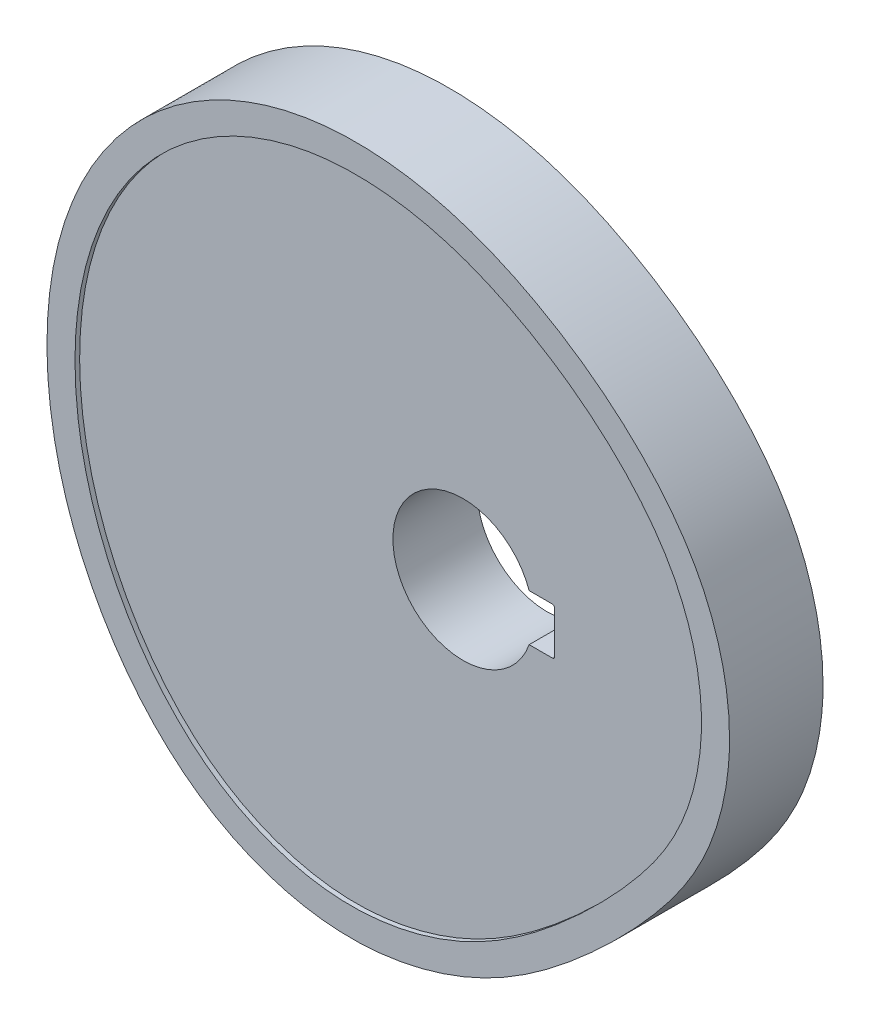
SolidWorks part; units mm, degrees
material "Plain Carbon Steel"
ref_plane "Front Plane" through (0, 0, 0) normal (0, 0, 1) x (1, 0, 0)
ref_plane "Top Plane" through (0, 0, 0) normal (0, 1, 0) x (1, 0, 0)
ref_plane "Right Plane" through (0, 0, 0) normal (1, 0, 0) x (0, 0, -1)
sketch "Displacement Sketch" plane through (0, 0, 0) normal (0, 0, 1) x (1, 0, 0)
  line L0 (0, 15) -> (0, 0) construction
  line L1 (0, 0) -> (47.1239, 0) construction
  line L2 (3.927, 0) -> (3.927, 15) construction
  line L3 (23.5619, 0) -> (23.5619, 15) construction
  line L4 (27.4889, 0) -> (27.4889, 15) construction
  line L5 (43.1969, 0) -> (43.1969, 15) construction
  line L6 (47.1239, 0) -> (47.1239, 15) construction
  line L7 (0, 0) -> (3.927, 0)
  line L8 (27.4889, 15) -> (23.5619, 15)
  line L9 (43.1969, 0) -> (47.1239, 0)
  spline S0 degree 4 poles (1.962, -0.0967) (2.0251, -0.0879) (2.1497, -0.0715) (2.3802, -0.0441) (2.7786, -0.0172) (3.1491, -0.0023) (3.8234, 0.0011) (4.1519, -0.0013) (4.7825, 0.0037) (5.2973, 0.0292) (5.8993, 0.0828) (6.4992, 0.198) (7.1843, 0.4092) (7.8229, 0.6945) (8.5028, 1.0958) (9.2434, 1.664) (10.1514, 2.5325) (11.1276, 3.6845) (12.1583, 5.0983) (13.2223, 6.6951) (14.2666, 8.3049) (15.3308, 9.9017) (16.361, 11.3155) (17.3382, 12.4675) (18.2447, 13.336) (18.9876, 13.9042) (19.6636, 14.3055) (20.2354, 14.5584) (20.6913, 14.7109) (21.0546, 14.8041) (21.3223, 14.8591) (21.5625, 14.8998) (21.7937, 14.9296) (22.0274, 14.9566) (22.3642, 14.9781) (22.6856, 14.9963) (23.3417, 15.0013) (23.6628, 14.9989) (24.3418, 15.0023) (24.7635, 15.0193) (25.1747, 15.049) (25.3985, 15.0791) (25.5259, 15.0967) knots 0 0 0 0 0 0.008159 0.016318 0.032637 0.048955 0.065274 0.0892 0.101163 0.113126 0.142767 0.163984 0.185201 0.206418 0.236195 0.268021 0.309045 0.372696 0.436348 0.5 0.563652 0.627304 0.690955 0.731979 0.763805 0.793582 0.814799 0.836016 0.846625 0.857233 0.864643 0.872053 0.879463 0.886874 0.898837 0.9108 0.934726 0.951045 0.967363 0.983682 1 1 1 1 1 construction
  spline S1 degree 4 poles (3.927, 0) (4.0838, 0) (4.3123, 0) (4.7825, 0.0037) (5.2973, 0.0292) (5.8993, 0.0828) (6.4992, 0.198) (7.1843, 0.4092) (7.8229, 0.6945) (8.5028, 1.0958) (9.2434, 1.664) (10.1514, 2.5325) (11.1276, 3.6845) (12.1583, 5.0983) (13.2223, 6.6951) (14.2666, 8.3049) (15.3308, 9.9017) (16.361, 11.3155) (17.3382, 12.4675) (18.2447, 13.336) (18.9876, 13.9042) (19.6636, 14.3055) (20.2354, 14.5584) (20.6913, 14.7109) (21.0546, 14.8041) (21.3223, 14.8591) (21.5625, 14.8998) (21.7937, 14.9296) (22.0274, 14.9566) (22.3642, 14.9781) (22.6856, 14.9963) (23.1748, 15) (23.4052, 15) (23.5619, 15) knots 0.065274 0.065274 0.065274 0.065274 0.065274 0.0892 0.101163 0.113126 0.142767 0.163984 0.185201 0.206418 0.236195 0.268021 0.309045 0.372696 0.436348 0.5 0.563652 0.627304 0.690955 0.731979 0.763805 0.793582 0.814799 0.836016 0.846625 0.857233 0.864643 0.872053 0.879463 0.886874 0.898837 0.9108 0.934726 0.934726 0.934726 0.934726 0.934726
  spline S2 degree 4 poles (25.917, 15.0967) (25.9672, 15.0879) (26.0664, 15.0716) (26.2503, 15.0442) (26.5692, 15.0173) (26.8684, 15.0023) (27.398, 14.9989) (27.6696, 15.0012) (28.1638, 14.9965) (28.4688, 14.9775) (28.7956, 14.949) (29.0691, 14.9044) (29.3652, 14.8416) (29.6303, 14.7623) (29.8895, 14.6683) (30.1363, 14.5572) (30.3781, 14.4298) (30.708, 14.2278) (31.1287, 13.9151) (31.7056, 13.3799) (32.4321, 12.5171) (33.1948, 11.3999) (33.9837, 10.0588) (34.759, 8.6207) (35.5133, 7.1717) (36.2737, 5.7258) (37.0683, 4.2981) (37.8437, 3.0586) (38.5964, 2.0494) (39.2866, 1.3197) (39.8479, 0.8516) (40.4053, 0.501) (40.8925, 0.2823) (41.3433, 0.149) (41.8164, 0.0573) (42.2412, 0.0166) (42.6103, 0.0017) (43.0977, -0.0005) (43.3551, 0.0006) (43.8251, -0.0023) (44.1115, -0.0173) (44.4386, -0.0442) (44.6184, -0.0716) (44.7185, -0.0879) (44.7693, -0.0967) knots 0 0 0 0 0 0.007472 0.014944 0.029888 0.044832 0.059777 0.081272 0.09202 0.102768 0.114604 0.126441 0.136767 0.147094 0.15742 0.167746 0.178072 0.188398 0.21612 0.247099 0.297177 0.359134 0.421092 0.48305 0.545008 0.606966 0.668924 0.730882 0.766656 0.797635 0.820922 0.841574 0.866069 0.878735 0.891402 0.915813 0.928018 0.940223 0.955168 0.970112 0.985056 0.992528 1 1 1 1 1 construction
  spline S3 degree 4 poles (27.4889, 15) (27.6137, 15) (27.7971, 15) (28.1638, 14.9965) (28.4688, 14.9775) (28.7956, 14.949) (29.0691, 14.9044) (29.3652, 14.8416) (29.6303, 14.7623) (29.8895, 14.6683) (30.1363, 14.5572) (30.3781, 14.4298) (30.708, 14.2278) (31.1287, 13.9151) (31.7056, 13.3799) (32.4321, 12.5171) (33.1948, 11.3999) (33.9837, 10.0588) (34.759, 8.6207) (35.5133, 7.1717) (36.2737, 5.7258) (37.0683, 4.2981) (37.8437, 3.0586) (38.5964, 2.0494) (39.2866, 1.3197) (39.8479, 0.8516) (40.4053, 0.501) (40.8925, 0.2823) (41.3433, 0.149) (41.8164, 0.0573) (42.2412, 0.0166) (42.6103, 0.0017) (42.9834, 0) (43.1261, 0) (43.1969, 0) knots 0.059777 0.059777 0.059777 0.059777 0.059777 0.081272 0.09202 0.102768 0.114604 0.126441 0.136767 0.147094 0.15742 0.167746 0.178072 0.188398 0.21612 0.247099 0.297177 0.359134 0.421092 0.48305 0.545008 0.606966 0.668924 0.730882 0.766656 0.797635 0.820922 0.841574 0.866069 0.878735 0.891402 0.915813 0.928018 0.940223 0.940223 0.940223 0.940223 0.940223
  dimension "D1" = 15
  dimension "D2" = 47.1239
  dimension "D3" = 3.927
  dimension "D4" = 19.635
  dimension "D5" = 3.927
  dimension "D6" = 15.708
  dimension "D7" = 3.927
sketch "Velocity Sketch" plane through (0, 0, 0) normal (0, 0, 1) x (1, 0, 0)
  line L0 (0, -15) -> (0, -65) construction
  line L1 (0, -40) -> (47.1239, -40) construction
  line L2 (3.927, -15) -> (3.927, -65) construction
  line L3 (23.5619, -15) -> (23.5619, -65) construction
  line L4 (27.4889, -15) -> (27.4889, -65) construction
  line L5 (43.1969, -15) -> (43.1969, -65) construction
  line L6 (47.1239, -15) -> (47.1239, -65) construction
  line L7 (0, -40) -> (3.927, -40)
  line L8 (23.5619, -40) -> (27.4889, -40)
  line L9 (43.1969, -40) -> (47.1239, -40)
  spline S0 degree 4 poles (1.9635, -38.9057) (2.0257, -38.9728) (2.1526, -39.1046) (2.3179, -39.263) (2.5282, -39.4396) (2.7124, -39.5752) (2.8656, -39.6755) (3.0312, -39.7696) (3.21, -39.8541) (3.378, -39.9155) (3.5323, -39.9566) (3.6606, -39.9808) (3.7704, -39.9939) (3.8976, -40.0012) (3.9765, -40.0003) (4.0914, -39.9931) (4.2047, -39.9788) (4.3113, -39.9585) (4.4273, -39.9287) (4.5497, -39.8882) (4.6855, -39.8341) (4.8338, -39.7637) (5.0005, -39.6692) (5.2228, -39.5203) (5.4703, -39.3234) (5.7369, -39.0742) (6.0182, -38.7713) (6.2635, -38.4767) (6.4789, -38.1966) (6.7119, -37.8755) (6.9601, -37.5119) (7.2378, -37.08) (7.6188, -36.4531) (8.0578, -35.69) (8.695, -34.5334) (9.3923, -33.2428) (10.1106, -31.9631) (10.8521, -30.798) (11.4447, -29.9912) (12.0701, -29.306) (12.6823, -28.8165) (13.3594, -28.5265) (13.9982, -28.5224) (14.4931, -28.6816) (14.9938, -28.9673) (15.4821, -29.3759) (16.0352, -29.9801) (16.6301, -30.7877) (17.3726, -31.9534) (18.0917, -33.2337) (18.7893, -34.5249) (19.4267, -35.6821) (19.8657, -36.4456) (20.2468, -37.073) (20.5641, -37.567) (20.8732, -38.0148) (21.1744, -38.4151) (21.4671, -38.7672) (21.7491, -39.0713) (22.0564, -39.3589) (22.3514, -39.5861) (22.6045, -39.7396) (22.8026, -39.8338) (22.9386, -39.888) (23.0611, -39.9286) (23.1771, -39.9584) (23.2842, -39.9788) (23.3789, -39.9907) (23.4581, -39.9971) (23.5401, -40.0006) (23.6106, -40) (23.7191, -39.9939) (23.8283, -39.9808) (23.9566, -39.9566) (24.111, -39.9155) (24.322, -39.8383) (24.5805, -39.7075) (24.8544, -39.5266) (25.138, -39.2946) (25.3363, -39.1046) (25.4632, -38.9728) (25.5254, -38.9057) knots 0 0 0 0 0 0.010194 0.020387 0.025484 0.030581 0.035677 0.040774 0.046689 0.052603 0.05556 0.058517 0.061474 0.064432 0.068544 0.0706 0.072656 0.076768 0.08088 0.083926 0.086973 0.093066 0.099159 0.105252 0.116762 0.128271 0.13978 0.15129 0.159464 0.167638 0.183987 0.200336 0.216684 0.249382 0.282079 0.347474 0.380171 0.412868 0.435887 0.458906 0.483278 0.499726 0.516191 0.528398 0.540605 0.563699 0.586794 0.619507 0.652221 0.717647 0.750361 0.783074 0.799431 0.815787 0.832144 0.8485 0.860048 0.871595 0.883143 0.89469 0.906897 0.913 0.916052 0.919104 0.92322 0.927336 0.929394 0.931452 0.93351 0.935568 0.938526 0.941483 0.94444 0.947397 0.953311 0.959226 0.969419 0.979613 0.989806 1 1 1 1 1 construction
  spline S1 degree 4 poles (3.927, -40) (3.9591, -40) (4.0069, -39.9984) (4.0914, -39.9931) (4.2047, -39.9788) (4.3113, -39.9585) (4.4273, -39.9287) (4.5497, -39.8882) (4.6855, -39.8341) (4.8338, -39.7637) (5.0005, -39.6692) (5.2228, -39.5203) (5.4703, -39.3234) (5.7369, -39.0742) (6.0182, -38.7713) (6.2635, -38.4767) (6.4789, -38.1966) (6.7119, -37.8755) (6.9601, -37.5119) (7.2378, -37.08) (7.6188, -36.4531) (8.0578, -35.69) (8.695, -34.5334) (9.3923, -33.2428) (10.1106, -31.9631) (10.8521, -30.798) (11.4447, -29.9912) (12.0701, -29.306) (12.6823, -28.8165) (13.3594, -28.5265) (13.9982, -28.5224) (14.4931, -28.6816) (14.9938, -28.9673) (15.4821, -29.3759) (16.0352, -29.9801) (16.6301, -30.7877) (17.3726, -31.9534) (18.0917, -33.2337) (18.7893, -34.5249) (19.4267, -35.6821) (19.8657, -36.4456) (20.2468, -37.073) (20.5641, -37.567) (20.8732, -38.0148) (21.1744, -38.4151) (21.4671, -38.7672) (21.7491, -39.0713) (22.0564, -39.3589) (22.3514, -39.5861) (22.6045, -39.7396) (22.8026, -39.8338) (22.9386, -39.888) (23.0611, -39.9286) (23.1771, -39.9584) (23.2842, -39.9788) (23.3789, -39.9907) (23.4581, -39.9971) (23.5136, -39.9995) (23.5459, -40) (23.5619, -40) knots 0.064432 0.064432 0.064432 0.064432 0.064432 0.068544 0.0706 0.072656 0.076768 0.08088 0.083926 0.086973 0.093066 0.099159 0.105252 0.116762 0.128271 0.13978 0.15129 0.159464 0.167638 0.183987 0.200336 0.216684 0.249382 0.282079 0.347474 0.380171 0.412868 0.435887 0.458906 0.483278 0.499726 0.516191 0.528398 0.540605 0.563699 0.586794 0.619507 0.652221 0.717647 0.750361 0.783074 0.799431 0.815787 0.832144 0.8485 0.860048 0.871595 0.883143 0.89469 0.906897 0.913 0.916052 0.919104 0.92322 0.927336 0.929394 0.931452 0.93351 0.935568 0.935568 0.935568 0.935568 0.935568
  spline S2 degree 4 poles (25.9181, -41.3678) (25.969, -41.2822) (26.0474, -41.155) (26.1567, -40.9884) (26.3034, -40.7872) (26.428, -40.6317) (26.5612, -40.4834) (26.7044, -40.3447) (26.8491, -40.2282) (26.9938, -40.1353) (27.1202, -40.0746) (27.2225, -40.0387) (27.3087, -40.0172) (27.3821, -40.0055) (27.4558, -39.9999) (27.5062, -39.9994) (27.5651, -40.003) (27.6216, -40.0095) (27.6752, -40.0191) (27.7266, -40.0316) (27.79, -40.0509) (27.8853, -40.0869) (28.0075, -40.1485) (28.1907, -40.2707) (28.3839, -40.4445) (28.5692, -40.6505) (28.7482, -40.8845) (28.8972, -41.1024) (29.0371, -41.3263) (29.1693, -41.5547) (29.3267, -41.8447) (29.5183, -42.2252) (29.738, -42.6988) (29.9816, -43.2668) (30.2236, -43.8681) (30.5135, -44.6245) (30.8469, -45.5378) (31.2234, -46.6076) (31.6487, -47.832) (32.0801, -49.0542) (32.4735, -50.118) (32.8326, -51.0215) (33.142, -51.7326) (33.3888, -52.2556) (33.6408, -52.7378) (33.8982, -53.1762) (34.223, -53.6432) (34.5556, -54.0066) (34.9078, -54.2495) (35.2458, -54.3293) (35.458, -54.327) (35.7081, -54.2632) (35.9731, -54.1157) (36.2611, -53.8668) (36.5554, -53.5158) (36.8301, -53.1086) (37.0915, -52.6536) (37.3438, -52.1599) (37.5898, -51.63) (37.8954, -50.918) (38.2495, -50.0196) (38.6386, -48.9625) (39.0662, -47.7483) (39.4887, -46.5322) (39.8632, -45.4699) (40.1952, -44.5632) (40.4842, -43.8123) (40.7255, -43.2156) (40.9683, -42.653) (41.187, -42.1848) (41.3776, -41.8095) (41.5335, -41.5246) (41.6646, -41.3002) (41.8032, -41.0803) (41.9509, -40.8664) (42.1281, -40.6369) (42.3115, -40.4352) (42.5023, -40.2652) (42.6833, -40.1457) (42.8038, -40.0854) (42.8984, -40.0501) (42.9739, -40.0273) (43.0476, -40.0102) (43.1489, -40) (43.2166, -39.9988) (43.3032, -40.0055) (43.3772, -40.0172) (43.4633, -40.0387) (43.5656, -40.0746) (43.6921, -40.1353) (43.8367, -40.2282) (43.9814, -40.3447) (44.1247, -40.4834) (44.2578, -40.6317) (44.3824, -40.7872) (44.5292, -40.9884) (44.6384, -41.155) (44.7169, -41.2822) (44.7677, -41.3678) knots 0 0 0 0 0 0.010463 0.015694 0.020925 0.026157 0.031388 0.03662 0.041851 0.045635 0.049419 0.051311 0.053203 0.055095 0.056987 0.058388 0.05979 0.061191 0.062592 0.063993 0.065395 0.068197 0.073266 0.078335 0.088472 0.095404 0.102336 0.109267 0.116199 0.123131 0.130063 0.143926 0.160948 0.17797 0.194992 0.212014 0.246057 0.280101 0.314145 0.348188 0.382232 0.399254 0.416276 0.429638 0.443 0.456362 0.469724 0.489196 0.494701 0.500206 0.505766 0.511326 0.521544 0.531762 0.545538 0.559313 0.573088 0.586864 0.60377 0.620676 0.654487 0.688299 0.722111 0.755922 0.789734 0.80664 0.823546 0.840451 0.857357 0.871007 0.877832 0.884657 0.891482 0.898307 0.905132 0.911957 0.921925 0.926909 0.931893 0.934673 0.936063 0.937453 0.940233 0.943013 0.944905 0.946797 0.948689 0.950581 0.954365 0.958149 0.96338 0.968612 0.973843 0.979075 0.984306 0.989537 1 1 1 1 1 construction
  spline S3 degree 4 poles (27.4889, -40) (27.5008, -40) (27.5245, -40.0005) (27.5651, -40.003) (27.6216, -40.0095) (27.6752, -40.0191) (27.7266, -40.0316) (27.79, -40.0509) (27.8853, -40.0869) (28.0075, -40.1485) (28.1907, -40.2707) (28.3839, -40.4445) (28.5692, -40.6505) (28.7482, -40.8845) (28.8972, -41.1024) (29.0371, -41.3263) (29.1693, -41.5547) (29.3267, -41.8447) (29.5183, -42.2252) (29.738, -42.6988) (29.9816, -43.2668) (30.2236, -43.8681) (30.5135, -44.6245) (30.8469, -45.5378) (31.2234, -46.6076) (31.6487, -47.832) (32.0801, -49.0542) (32.4735, -50.118) (32.8326, -51.0215) (33.142, -51.7326) (33.3888, -52.2556) (33.6408, -52.7378) (33.8982, -53.1762) (34.223, -53.6432) (34.5556, -54.0066) (34.9078, -54.2495) (35.2458, -54.3293) (35.458, -54.327) (35.7081, -54.2632) (35.9731, -54.1157) (36.2611, -53.8668) (36.5554, -53.5158) (36.8301, -53.1086) (37.0915, -52.6536) (37.3438, -52.1599) (37.5898, -51.63) (37.8954, -50.918) (38.2495, -50.0196) (38.6386, -48.9625) (39.0662, -47.7483) (39.4887, -46.5322) (39.8632, -45.4699) (40.1952, -44.5632) (40.4842, -43.8123) (40.7255, -43.2156) (40.9683, -42.653) (41.187, -42.1848) (41.3776, -41.8095) (41.5335, -41.5246) (41.6646, -41.3002) (41.8032, -41.0803) (41.9509, -40.8664) (42.1281, -40.6369) (42.3115, -40.4352) (42.5023, -40.2652) (42.6833, -40.1457) (42.8038, -40.0854) (42.8984, -40.0501) (42.9739, -40.0273) (43.0476, -40.0102) (43.1272, -40.0021) (43.1735, -40) (43.1969, -40) knots 0.056987 0.056987 0.056987 0.056987 0.056987 0.058388 0.05979 0.061191 0.062592 0.063993 0.065395 0.068197 0.073266 0.078335 0.088472 0.095404 0.102336 0.109267 0.116199 0.123131 0.130063 0.143926 0.160948 0.17797 0.194992 0.212014 0.246057 0.280101 0.314145 0.348188 0.382232 0.399254 0.416276 0.429638 0.443 0.456362 0.469724 0.489196 0.494701 0.500206 0.505766 0.511326 0.521544 0.531762 0.545538 0.559313 0.573088 0.586864 0.60377 0.620676 0.654487 0.688299 0.722111 0.755922 0.789734 0.80664 0.823546 0.840451 0.857357 0.871007 0.877832 0.884657 0.891482 0.898307 0.905132 0.911957 0.921925 0.926909 0.931893 0.934673 0.936063 0.937453 0.940233 0.943013 0.943013 0.943013 0.943013 0.943013
  point P15 (23.5619, -40)
  point P27 (43.1969, -40)
  point P28 (3.927, -40)
  point P35 (27.4889, -40)
  dimension "D1" = 50
  dimension "D2" = 15
  dimension "D3" = 47.1239
sketch "Acceleration Sketch" plane through (0, 0, 0) normal (0, 0, 1) x (1, 0, 0)
  line L0 (0, -80) -> (0, -130) construction
  line L1 (0, -15) -> (0, -65) construction
  line L2 (3.927, -80) -> (3.927, -130) construction
  line L3 (23.5619, -80) -> (23.5619, -130) construction
  line L4 (27.4889, -80) -> (27.4889, -130) construction
  line L5 (43.1969, -80) -> (43.1969, -130) construction
  line L6 (47.1239, -80) -> (47.1239, -130) construction
  line L7 (0, -105) -> (47.1239, -105) construction
  spline S0 degree 4 poles (2.572, -110.7775) (2.5826, -110.7352) (2.6049, -110.6462) (2.6568, -110.4348) (2.7247, -110.1667) (2.8631, -109.5866) (2.9168, -109.376) (3.1103, -108.5487) (3.2451, -107.9915) (3.7647, -105.7173) (3.9235, -105.0128) (4.4418, -102.7383) (4.726, -101.5165) (5.0905, -99.9824) (5.4257, -98.6411) (5.7628, -97.3573) (6.0541, -96.3347) (6.324, -95.4451) (6.5477, -94.7627) (6.7807, -94.1024) (7.0182, -93.4965) (7.2387, -92.994) (7.4321, -92.6044) (7.6103, -92.2868) (7.7652, -92.0405) (7.9385, -91.8029) (8.1364, -91.5783) (8.3751, -91.3792) (8.6628, -91.239) (9.0399, -91.2355) (9.3821, -91.4294) (9.658, -91.7026) (9.9031, -92.031) (10.1006, -92.3508) (10.3757, -92.8619) (10.6941, -93.5774) (11.0415, -94.5007) (11.4096, -95.6315) (11.7539, -96.8019) (12.0819, -98.0088) (12.4807, -99.5681) (12.9408, -101.482) (13.4552, -103.72) (14.0337, -106.28) (14.5481, -108.518) (15.0082, -110.4319) (15.4071, -111.9912) (15.735, -113.1981) (16.0793, -114.3685) (16.4474, -115.4993) (16.7948, -116.4226) (17.1133, -117.1381) (17.3883, -117.6492) (17.5858, -117.969) (17.831, -118.2974) (18.1068, -118.5706) (18.449, -118.7645) (18.8261, -118.761) (19.1138, -118.6208) (19.3525, -118.4218) (19.5505, -118.197) (19.7664, -117.9009) (19.991, -117.5251) (20.221, -117.0728) (20.4706, -116.5036) (20.7083, -115.8976) (20.9412, -115.2374) (21.1649, -114.5549) (21.4349, -113.6653) (21.7261, -112.6427) (22.0633, -111.3589) (22.3985, -110.0176) (22.763, -108.4835) (23.0471, -107.2617) (23.5654, -104.9872) (23.7242, -104.2827) (24.2438, -102.0085) (24.3787, -101.4513) (24.5722, -100.624) (24.6258, -100.4134) (24.7642, -99.8333) (24.8321, -99.5652) (24.884, -99.3538) (24.9063, -99.2648) (24.917, -99.2225) knots 0 0 0 0 0 0.002588 0.005177 0.010354 0.020707 0.025884 0.031061 0.041414 0.082829 0.103192 0.123556 0.14392 0.164284 0.184648 0.205012 0.215194 0.225376 0.235558 0.24574 0.253858 0.261975 0.266034 0.270093 0.274152 0.278211 0.282468 0.286725 0.291483 0.295696 0.302677 0.307932 0.313188 0.318443 0.323699 0.340297 0.356895 0.373493 0.390091 0.408409 0.426727 0.463364 0.5 0.536636 0.573273 0.591591 0.609909 0.626507 0.643105 0.659703 0.676301 0.681557 0.686812 0.692068 0.697323 0.704304 0.708517 0.713275 0.717532 0.721789 0.725848 0.729907 0.738025 0.746142 0.75426 0.764442 0.774624 0.784806 0.794988 0.815352 0.835716 0.85608 0.876444 0.896808 0.917171 0.958586 0.968939 0.974116 0.979293 0.989646 0.994823 0.997412 1 1 1 1 1 construction
  spline S1 degree 4 poles (3.927, -105) (3.9944, -104.7033) (4.1329, -104.0938) (4.4418, -102.7383) (4.726, -101.5165) (5.0905, -99.9824) (5.4257, -98.6411) (5.7628, -97.3573) (6.0541, -96.3347) (6.324, -95.4451) (6.5477, -94.7627) (6.7807, -94.1024) (7.0182, -93.4965) (7.2387, -92.994) (7.4321, -92.6044) (7.6103, -92.2868) (7.7652, -92.0405) (7.9385, -91.8029) (8.1364, -91.5783) (8.3751, -91.3792) (8.6628, -91.239) (9.0399, -91.2355) (9.3821, -91.4294) (9.658, -91.7026) (9.9031, -92.031) (10.1006, -92.3508) (10.3757, -92.8619) (10.6941, -93.5774) (11.0415, -94.5007) (11.4096, -95.6315) (11.7539, -96.8019) (12.0819, -98.0088) (12.4807, -99.5681) (12.9408, -101.482) (13.4552, -103.72) (14.0337, -106.28) (14.5481, -108.518) (15.0082, -110.4319) (15.4071, -111.9912) (15.735, -113.1981) (16.0793, -114.3685) (16.4474, -115.4993) (16.7948, -116.4226) (17.1133, -117.1381) (17.3883, -117.6492) (17.5858, -117.969) (17.831, -118.2974) (18.1068, -118.5706) (18.449, -118.7645) (18.8261, -118.761) (19.1138, -118.6208) (19.3525, -118.4218) (19.5505, -118.197) (19.7664, -117.9009) (19.991, -117.5251) (20.221, -117.0728) (20.4706, -116.5036) (20.7083, -115.8976) (20.9412, -115.2374) (21.1649, -114.5549) (21.4349, -113.6653) (21.7261, -112.6427) (22.0633, -111.3589) (22.3985, -110.0176) (22.763, -108.4835) (23.0471, -107.2617) (23.356, -105.9062) (23.4945, -105.2967) (23.5619, -105) knots 0.082829 0.082829 0.082829 0.082829 0.082829 0.103192 0.123556 0.14392 0.164284 0.184648 0.205012 0.215194 0.225376 0.235558 0.24574 0.253858 0.261975 0.266034 0.270093 0.274152 0.278211 0.282468 0.286725 0.291483 0.295696 0.302677 0.307932 0.313188 0.318443 0.323699 0.340297 0.356895 0.373493 0.390091 0.408409 0.426727 0.463364 0.5 0.536636 0.573273 0.591591 0.609909 0.626507 0.643105 0.659703 0.676301 0.681557 0.686812 0.692068 0.697323 0.704304 0.708517 0.713275 0.717532 0.721789 0.725848 0.729907 0.738025 0.746142 0.75426 0.764442 0.774624 0.784806 0.794988 0.815352 0.835716 0.85608 0.876444 0.896808 0.917171 0.917171 0.917171 0.917171 0.917171
  spline S2 degree 4 poles (26.4484, -96.3102) (26.5118, -96.8222) (26.5658, -97.2281) (26.8032, -99.1812) (26.9742, -100.5869) (27.3892, -104.1392) (27.5686, -105.6882) (27.9878, -109.2775) (28.2426, -111.3928) (28.6075, -114.3425) (28.9332, -116.7713) (29.3318, -119.5372) (29.6889, -121.6296) (30.0509, -123.449) (30.3524, -124.5941) (30.5472, -125.2296) (30.7103, -125.6432) (30.821, -125.8896) (30.926, -126.0792) (31.0123, -126.2131) (31.0985, -126.3183) (31.1798, -126.3936) (31.2441, -126.4375) (31.2991, -126.4643) (31.3487, -126.4798) (31.3966, -126.4868) (31.4431, -126.4862) (31.491, -126.4779) (31.541, -126.4609) (31.5967, -126.4322) (31.6626, -126.3849) (31.7478, -126.3032) (31.8681, -126.1482) (32.0585, -125.8141) (32.3727, -125.0186) (32.7489, -123.6119) (33.1471, -121.6395) (33.5462, -119.2173) (33.9186, -116.6385) (34.2594, -114.0551) (34.5809, -111.4694) (34.8901, -108.8821) (35.1927, -106.2941) (35.4931, -103.7059) (35.7957, -101.1179) (36.1049, -98.5306) (36.4264, -95.9449) (36.7673, -93.3615) (37.1397, -90.7827) (37.5387, -88.3605) (37.9369, -86.3881) (38.3131, -84.9814) (38.6274, -84.1859) (38.8178, -83.8518) (38.9381, -83.6968) (39.0232, -83.6151) (39.0891, -83.5678) (39.1448, -83.5391) (39.1948, -83.5221) (39.2428, -83.5138) (39.2893, -83.5132) (39.3371, -83.5202) (39.3867, -83.5357) (39.4417, -83.5624) (39.506, -83.6068) (39.5872, -83.6808) (39.7, -83.8211) (39.8275, -84.031) (39.9606, -84.3179) (40.1387, -84.7711) (40.3334, -85.4056) (40.635, -86.5512) (40.9969, -88.3703) (41.354, -90.4629) (41.7526, -93.2287) (42.0783, -95.6575) (42.4432, -98.6072) (42.6981, -100.7225) (43.1172, -104.3118) (43.2966, -105.8608) (43.7116, -109.4131) (43.8826, -110.8188) (44.12, -112.7719) (44.174, -113.1778) (44.2375, -113.6898) knots 0 0 0 0 0 0.013744 0.027488 0.054976 0.082464 0.107561 0.132658 0.157755 0.182852 0.207948 0.233045 0.258142 0.266928 0.275713 0.279145 0.282576 0.284145 0.285714 0.287455 0.28853 0.289309 0.289879 0.290393 0.290836 0.291269 0.291702 0.292145 0.29267 0.293258 0.294064 0.295205 0.297118 0.300661 0.308565 0.327485 0.35213 0.376775 0.40142 0.426065 0.45071 0.475355 0.5 0.524645 0.54929 0.573935 0.59858 0.623225 0.64787 0.672515 0.691435 0.699339 0.702882 0.704795 0.705936 0.706742 0.70733 0.707855 0.708298 0.708731 0.709164 0.709607 0.710121 0.710691 0.71147 0.712545 0.714286 0.717424 0.720855 0.724287 0.733072 0.741858 0.766955 0.792052 0.817148 0.842245 0.867342 0.892439 0.917536 0.945024 0.972512 0.986256 1 1 1 1 1 construction
  spline S3 degree 4 poles (27.4889, -105) (27.553, -105.5502) (27.6807, -106.6482) (27.9878, -109.2775) (28.2426, -111.3928) (28.6075, -114.3425) (28.9332, -116.7713) (29.3318, -119.5372) (29.6889, -121.6296) (30.0509, -123.449) (30.3524, -124.5941) (30.5472, -125.2296) (30.7103, -125.6432) (30.821, -125.8896) (30.926, -126.0792) (31.0123, -126.2131) (31.0985, -126.3183) (31.1798, -126.3936) (31.2441, -126.4375) (31.2991, -126.4643) (31.3487, -126.4798) (31.3966, -126.4868) (31.4431, -126.4862) (31.491, -126.4779) (31.541, -126.4609) (31.5967, -126.4322) (31.6626, -126.3849) (31.7478, -126.3032) (31.8681, -126.1482) (32.0585, -125.8141) (32.3727, -125.0186) (32.7489, -123.6119) (33.1471, -121.6395) (33.5462, -119.2173) (33.9186, -116.6385) (34.2594, -114.0551) (34.5809, -111.4694) (34.8901, -108.8821) (35.1927, -106.2941) (35.4931, -103.7059) (35.7957, -101.1179) (36.1049, -98.5306) (36.4264, -95.9449) (36.7673, -93.3615) (37.1397, -90.7827) (37.5387, -88.3605) (37.9369, -86.3881) (38.3131, -84.9814) (38.6274, -84.1859) (38.8178, -83.8518) (38.9381, -83.6968) (39.0232, -83.6151) (39.0891, -83.5678) (39.1448, -83.5391) (39.1948, -83.5221) (39.2428, -83.5138) (39.2893, -83.5132) (39.3371, -83.5202) (39.3867, -83.5357) (39.4417, -83.5624) (39.506, -83.6068) (39.5872, -83.6808) (39.7, -83.8211) (39.8275, -84.031) (39.9606, -84.3179) (40.1387, -84.7711) (40.3334, -85.4056) (40.635, -86.5512) (40.9969, -88.3703) (41.354, -90.4629) (41.7526, -93.2287) (42.0783, -95.6575) (42.4432, -98.6072) (42.6981, -100.7225) (43.0051, -103.3518) (43.1329, -104.4498) (43.1969, -105) knots 0.082464 0.082464 0.082464 0.082464 0.082464 0.107561 0.132658 0.157755 0.182852 0.207948 0.233045 0.258142 0.266928 0.275713 0.279145 0.282576 0.284145 0.285714 0.287455 0.28853 0.289309 0.289879 0.290393 0.290836 0.291269 0.291702 0.292145 0.29267 0.293258 0.294064 0.295205 0.297118 0.300661 0.308565 0.327485 0.35213 0.376775 0.40142 0.426065 0.45071 0.475355 0.5 0.524645 0.54929 0.573935 0.59858 0.623225 0.64787 0.672515 0.691435 0.699339 0.702882 0.704795 0.705936 0.706742 0.70733 0.707855 0.708298 0.708731 0.709164 0.709607 0.710121 0.710691 0.71147 0.712545 0.714286 0.717424 0.720855 0.724287 0.733072 0.741858 0.766955 0.792052 0.817148 0.842245 0.867342 0.892439 0.917536 0.917536 0.917536 0.917536 0.917536
  point P30 (3.927, -105)
  dimension "D1" = 15
sketch "Cam Profile Sketch" plane through (0, 0, 0) normal (0, 0, 1) x (1, 0, 0)
  line L0 (-49, 0) -> (-93, 0) construction
  line L3 (-49, 0) -> (-87.1051, -22) construction
  circle A1 centre (-49, 0) radius 29 construction
  arc A2 (-93, 0) -> (-87.1051, -22) centre (-49, 0) ccw
  arc A3 (-23.8853, -14.5) -> (-23.8853, 14.5) centre (-49, 0) ccw
  spline S0 degree 4 poles (-21.0816, 7.4807) (-21.1347, 7.7136) (-21.2473, 8.178) (-21.4357, 8.8697) (-21.7242, 9.7809) (-22.0073, 10.5659) (-22.2705, 11.2287) (-22.5025, 11.7733) (-22.6947, 12.2028) (-22.8944, 12.6284) (-23.1031, 13.0532) (-23.2883, 13.415) (-23.4527, 13.7251) (-23.6023, 13.9987) (-23.726, 14.2207) (-23.8638, 14.464) (-23.992, 14.6844) (-24.2319, 15.0878) (-24.4645, 15.4634) (-24.7034, 15.8366) (-24.9512, 16.2123) (-25.2035, 16.5831) (-25.4607, 16.9499) (-25.7512, 17.3524) (-26.2677, 18.0453) (-27.1324, 19.1368) (-28.4165, 20.6093) (-30.1456, 22.3683) (-31.9522, 24.0003) (-33.682, 25.4157) (-35.2829, 26.6203) (-36.7346, 27.637) (-38.214, 28.6) (-39.7256, 29.5117) (-41.2684, 30.3695) (-43.2348, 31.3707) (-45.6528, 32.452) (-48.5535, 33.523) (-51.6032, 34.3581) (-54.3423, 34.8797) (-57.1097, 35.211) (-59.8951, 35.3457) (-63.056, 35.2217) (-66.5557, 34.7132) (-69.9807, 33.8313) (-73.2889, 32.5802) (-76.4387, 30.9712) (-79.4088, 29.0105) (-82.1582, 26.7166) (-84.6496, 24.1145) (-86.8505, 21.2354) (-88.7264, 18.1351) (-90.2072, 14.9786) (-91.2012, 12.1859) (-91.847, 9.8314) (-92.2209, 8.1094) (-92.439, 6.9089) (-92.5993, 5.859) (-92.7156, 4.9622) (-92.7998, 4.1755) (-92.8596, 3.4999) (-92.9013, 2.9365) (-92.9298, 2.4854) (-92.9534, 2.0327) (-92.9723, 1.5812) (-92.9864, 1.1389) (-92.9957, 0.6708) (-93.0008, 0.1194) (-93.0002, -0.2419) (-92.9923, -0.953) (-92.9757, -1.5075) (-92.9508, -2.1317) (-92.9179, -2.734) (-92.877, -3.3425) (-92.8281, -3.9481) (-92.7715, -4.5539) (-92.7071, -5.1586) (-92.6171, -5.9135) (-92.4941, -6.8175) (-92.3525, -7.7188) (-92.193, -8.6171) (-92.0772, -9.2141) (-92.017, -9.5122) (-91.9863, -9.6611) knots 0 0 0 0 0 0.008336 0.016672 0.025009 0.033345 0.03745 0.041556 0.045661 0.049766 0.053872 0.057977 0.06003 0.062083 0.064135 0.066188 0.070099 0.07401 0.07792 0.081831 0.085742 0.089653 0.093564 0.097475 0.103059 0.11981 0.142146 0.165611 0.189076 0.204719 0.220116 0.235513 0.25091 0.266306 0.281703 0.2971 0.327893 0.358686 0.38948 0.407291 0.425102 0.455895 0.486688 0.517482 0.548275 0.579069 0.609862 0.640655 0.672207 0.70376 0.735312 0.766864 0.798416 0.82521 0.838607 0.852004 0.859892 0.86778 0.875668 0.883556 0.8875 0.891444 0.895388 0.899332 0.903276 0.90722 0.911164 0.915108 0.920414 0.92572 0.931025 0.936331 0.941637 0.946943 0.952248 0.957554 0.96286 0.968166 0.978777 0.989389 0.994694 1 1 1 1 1 construction
  spline S1 degree 4 poles (-23.8853, 14.5) (-23.9328, 14.5824) (-24.0277, 14.7445) (-24.2319, 15.0878) (-24.4645, 15.4634) (-24.7034, 15.8366) (-24.9512, 16.2123) (-25.2035, 16.5831) (-25.4607, 16.9499) (-25.7512, 17.3524) (-26.2677, 18.0453) (-27.1324, 19.1368) (-28.4165, 20.6093) (-30.1456, 22.3683) (-31.9522, 24.0003) (-33.682, 25.4157) (-35.2829, 26.6203) (-36.7346, 27.637) (-38.214, 28.6) (-39.7256, 29.5117) (-41.2684, 30.3695) (-43.2348, 31.3707) (-45.6528, 32.452) (-48.5535, 33.523) (-51.6032, 34.3581) (-54.3423, 34.8797) (-57.1097, 35.211) (-59.8951, 35.3457) (-63.056, 35.2217) (-66.5557, 34.7132) (-69.9807, 33.8313) (-73.2889, 32.5802) (-76.4387, 30.9712) (-79.4088, 29.0105) (-82.1582, 26.7166) (-84.6496, 24.1145) (-86.8505, 21.2354) (-88.7264, 18.1351) (-90.2072, 14.9786) (-91.2012, 12.1859) (-91.847, 9.8314) (-92.2209, 8.1094) (-92.439, 6.9089) (-92.5993, 5.859) (-92.7156, 4.9622) (-92.7998, 4.1755) (-92.8596, 3.4999) (-92.9013, 2.9365) (-92.9298, 2.4854) (-92.9534, 2.0327) (-92.9723, 1.5812) (-92.9864, 1.1389) (-92.9957, 0.6708) (-92.9992, 0.2901) (-93, 0.0959) (-93, 0) knots 0.066188 0.066188 0.066188 0.066188 0.066188 0.070099 0.07401 0.07792 0.081831 0.085742 0.089653 0.093564 0.097475 0.103059 0.11981 0.142146 0.165611 0.189076 0.204719 0.220116 0.235513 0.25091 0.266306 0.281703 0.2971 0.327893 0.358686 0.38948 0.407291 0.425102 0.455895 0.486688 0.517482 0.548275 0.579069 0.609862 0.640655 0.672207 0.70376 0.735312 0.766864 0.798416 0.82521 0.838607 0.852004 0.859892 0.86778 0.875668 0.883556 0.8875 0.891444 0.895388 0.899332 0.903276 0.90722 0.911164 0.915108 0.915108 0.915108 0.915108 0.915108
  spline S2 degree 4 poles (-21.5114, -8.9316) (-21.5618, -9.116) (-21.6673, -9.4835) (-21.8391, -10.0305) (-22.0947, -10.7517) (-22.3734, -11.4601) (-22.675, -12.1576) (-22.9554, -12.7549) (-23.21, -13.2631) (-23.4255, -13.6746) (-23.6039, -14.0037) (-23.8171, -14.3825) (-23.9437, -14.6021) (-24.1533, -14.9565) (-24.3405, -15.2639) (-24.5245, -15.5577) (-24.7154, -15.8558) (-24.9096, -16.152) (-25.204, -16.5908) (-25.5555, -17.0963) (-26.07, -17.8075) (-26.6555, -18.5744) (-27.2016, -19.2598) (-27.9845, -20.2063) (-28.905, -21.2718) (-29.9727, -22.445) (-31.1919, -23.7204) (-32.3132, -24.8484) (-33.3264, -25.8344) (-34.356, -26.8033) (-35.4027, -27.7536) (-36.4677, -28.6835) (-37.5521, -29.5906) (-38.6574, -30.4723) (-40.0665, -31.5389) (-41.5142, -32.5534) (-43.2999, -33.6987) (-45.4952, -34.9391) (-47.7646, -36.0414) (-50.4458, -37.085) (-53.2075, -37.8928) (-55.9852, -38.4418) (-58.8021, -38.7298) (-61.634, -38.7457) (-64.4538, -38.4832) (-67.3037, -37.9274) (-69.7768, -37.1729) (-71.8775, -36.3239) (-73.6249, -35.4667) (-75.324, -34.5176) (-76.9536, -33.4513) (-78.5066, -32.2766) (-79.9784, -31.0034) (-80.9649, -30.0639) (-81.7785, -29.2267) (-82.4351, -28.5089) (-82.9475, -27.9232) (-83.4441, -27.3299) (-83.925, -26.73) (-84.391, -26.1233) (-84.8413, -25.5121) (-85.2807, -24.8903) (-85.7062, -24.2635) (-86.123, -23.6232) (-86.4733, -23.0634) (-86.7658, -22.58) (-87.0529, -22.0915) (-87.2018, -21.8328) (-87.4828, -21.3358) (-87.7026, -20.9336) (-87.9376, -20.4943) (-88.1641, -20.0595) (-88.4424, -19.5117) (-88.7672, -18.8502) (-89.1335, -18.0721) (-89.535, -17.1752) (-89.8718, -16.384) (-90.1504, -15.7017) (-90.331, -15.2447) (-90.4199, -15.0157) (-90.4641, -14.9011) knots 0 0 0 0 0 0.008262 0.016523 0.024785 0.033047 0.041182 0.049318 0.053386 0.057454 0.061521 0.065589 0.069408 0.073227 0.077046 0.080865 0.084684 0.088503 0.092322 0.103716 0.111291 0.126441 0.134017 0.141592 0.16438 0.187294 0.202569 0.217845 0.233121 0.248396 0.263672 0.278948 0.294223 0.309499 0.324775 0.355326 0.370602 0.401153 0.433708 0.464259 0.49481 0.525362 0.555913 0.586464 0.617016 0.647567 0.6812 0.698016 0.714832 0.731649 0.765281 0.782098 0.798914 0.81573 0.824138 0.832546 0.840955 0.849363 0.857574 0.865785 0.873997 0.882208 0.890419 0.898631 0.906842 0.910948 0.915054 0.920363 0.925672 0.930981 0.93629 0.941599 0.946908 0.957527 0.968145 0.978763 0.989382 0.994691 1 1 1 1 1 construction
  spline S3 degree 4 poles (-23.8853, -14.5) (-23.9228, -14.565) (-23.9986, -14.695) (-24.1533, -14.9565) (-24.3405, -15.2639) (-24.5245, -15.5577) (-24.7154, -15.8558) (-24.9096, -16.152) (-25.204, -16.5908) (-25.5555, -17.0963) (-26.07, -17.8075) (-26.6555, -18.5744) (-27.2016, -19.2598) (-27.9845, -20.2063) (-28.905, -21.2718) (-29.9727, -22.445) (-31.1919, -23.7204) (-32.3132, -24.8484) (-33.3264, -25.8344) (-34.356, -26.8033) (-35.4027, -27.7536) (-36.4677, -28.6835) (-37.5521, -29.5906) (-38.6574, -30.4723) (-40.0665, -31.5389) (-41.5142, -32.5534) (-43.2999, -33.6987) (-45.4952, -34.9391) (-47.7646, -36.0414) (-50.4458, -37.085) (-53.2075, -37.8928) (-55.9852, -38.4418) (-58.8021, -38.7298) (-61.634, -38.7457) (-64.4538, -38.4832) (-67.3037, -37.9274) (-69.7768, -37.1729) (-71.8775, -36.3239) (-73.6249, -35.4667) (-75.324, -34.5176) (-76.9536, -33.4513) (-78.5066, -32.2766) (-79.9784, -31.0034) (-80.9649, -30.0639) (-81.7785, -29.2267) (-82.4351, -28.5089) (-82.9475, -27.9232) (-83.4441, -27.3299) (-83.925, -26.73) (-84.391, -26.1233) (-84.8413, -25.5121) (-85.2807, -24.8903) (-85.7062, -24.2635) (-86.123, -23.6232) (-86.4733, -23.0634) (-86.7658, -22.58) (-86.9827, -22.2109) (-87.0648, -22.0699) (-87.1051, -22) knots 0.065589 0.065589 0.065589 0.065589 0.065589 0.069408 0.073227 0.077046 0.080865 0.084684 0.088503 0.092322 0.103716 0.111291 0.126441 0.134017 0.141592 0.16438 0.187294 0.202569 0.217845 0.233121 0.248396 0.263672 0.278948 0.294223 0.309499 0.324775 0.355326 0.370602 0.401153 0.433708 0.464259 0.49481 0.525362 0.555913 0.586464 0.617016 0.647567 0.6812 0.698016 0.714832 0.731649 0.765281 0.782098 0.798914 0.81573 0.824138 0.832546 0.840955 0.849363 0.857574 0.865785 0.873997 0.882208 0.890419 0.898631 0.906842 0.910948 0.915054 0.915054 0.915054 0.915054 0.915054
  dimension "D2" = 29
  dimension "D1" = 49
  dimension "D3" = 44
  dimension "D6" = 30
  dimension "D8" = 180
sketch "Sketch9" plane through (0, 0, 0) normal (0, 0, 1) x (1, 0, 0)
  arc A0 (-23.8853, -14.5) -> (-23.8853, 14.5) centre (-49, 0) ccw construction
  arc A1 (-93, 0) -> (-87.1051, -22) centre (-49, 0) ccw construction
  spline S0 degree 3 poles (-20.328, -5.5157) (-19.7601, 1.2133) (-20.7522, 7.9128) (-23.7872, 14.9129) (-29.6952, 22.5982) (-38.8476, 29.6324) (-51.494, 35.0642) (-63.757, 35.8239) (-74.2988, 32.5141) (-82.056, 27.2941) (-88.2323, 19.843) (-92.1735, 10.4235) (-93.4584, -0.37) (-91.9816, -11.5244) (-86.9868, -23.6477) (-77.4972, -34.7141) (-62.0537, -40.1573) (-46.6106, -36.6949) (-35.7022, -28.4037) (-28.8891, -21.4716) (-24.7226, -16.1118) (-21.9581, -11.0938) (-20.328, -5.5157) (-19.7601, 1.2133) (-20.7522, 7.9128) knots -0.07558 -0.051175 -0.021273 0 0.037258 0.066322 0.099392 0.163632 0.215601 0.278636 0.320092 0.358809 0.399929 0.445527 0.490999 0.541318 0.591638 0.661938 0.72596 0.796842 0.859785 0.903869 0.92442 0.948825 0.978727 1 1.037258 1.066322 1.099392 only from (-20, 0) to (-20, 0)
  spline S1 degree 4 poles (-23.8853, 14.5) (-23.9328, 14.5824) (-24.0277, 14.7445) (-24.2319, 15.0878) (-24.4645, 15.4634) (-24.7034, 15.8366) (-24.9512, 16.2123) (-25.2035, 16.5831) (-25.4607, 16.9499) (-25.7512, 17.3524) (-26.2677, 18.0453) (-27.1324, 19.1368) (-28.4165, 20.6093) (-30.1456, 22.3683) (-31.9522, 24.0003) (-33.682, 25.4157) (-35.2829, 26.6203) (-36.7346, 27.637) (-38.214, 28.6) (-39.7256, 29.5117) (-41.2684, 30.3695) (-43.2348, 31.3707) (-45.6528, 32.452) (-48.5535, 33.523) (-51.6032, 34.3581) (-54.3423, 34.8797) (-57.1097, 35.211) (-59.8951, 35.3457) (-63.056, 35.2217) (-66.5557, 34.7132) (-69.9807, 33.8313) (-73.2889, 32.5802) (-76.4387, 30.9712) (-79.4088, 29.0105) (-82.1582, 26.7166) (-84.6496, 24.1145) (-86.8505, 21.2354) (-88.7264, 18.1351) (-90.2072, 14.9786) (-91.2012, 12.1859) (-91.847, 9.8314) (-92.2209, 8.1094) (-92.439, 6.9089) (-92.5993, 5.859) (-92.7156, 4.9622) (-92.7998, 4.1755) (-92.8596, 3.4999) (-92.9013, 2.9365) (-92.9298, 2.4854) (-92.9534, 2.0327) (-92.9723, 1.5812) (-92.9864, 1.1389) (-92.9957, 0.6708) (-92.9992, 0.2901) (-93, 0.0959) (-93, 0) knots 0.066188 0.066188 0.066188 0.066188 0.066188 0.070099 0.07401 0.07792 0.081831 0.085742 0.089653 0.093564 0.097475 0.103059 0.11981 0.142146 0.165611 0.189076 0.204719 0.220116 0.235513 0.25091 0.266306 0.281703 0.2971 0.327893 0.358686 0.38948 0.407291 0.425102 0.455895 0.486688 0.517482 0.548275 0.579069 0.609862 0.640655 0.672207 0.70376 0.735312 0.766864 0.798416 0.82521 0.838607 0.852004 0.859892 0.86778 0.875668 0.883556 0.8875 0.891444 0.895388 0.899332 0.903276 0.90722 0.911164 0.915108 0.915108 0.915108 0.915108 0.915108 construction
  spline S2 degree 4 poles (-23.8853, -14.5) (-23.9228, -14.565) (-23.9986, -14.695) (-24.1533, -14.9565) (-24.3405, -15.2639) (-24.5245, -15.5577) (-24.7154, -15.8558) (-24.9096, -16.152) (-25.204, -16.5908) (-25.5555, -17.0963) (-26.07, -17.8075) (-26.6555, -18.5744) (-27.2016, -19.2598) (-27.9845, -20.2063) (-28.905, -21.2718) (-29.9727, -22.445) (-31.1919, -23.7204) (-32.3132, -24.8484) (-33.3264, -25.8344) (-34.356, -26.8033) (-35.4027, -27.7536) (-36.4677, -28.6835) (-37.5521, -29.5906) (-38.6574, -30.4723) (-40.0665, -31.5389) (-41.5142, -32.5534) (-43.2999, -33.6987) (-45.4952, -34.9391) (-47.7646, -36.0414) (-50.4458, -37.085) (-53.2075, -37.8928) (-55.9852, -38.4418) (-58.8021, -38.7298) (-61.634, -38.7457) (-64.4538, -38.4832) (-67.3037, -37.9274) (-69.7768, -37.1729) (-71.8775, -36.3239) (-73.6249, -35.4667) (-75.324, -34.5176) (-76.9536, -33.4513) (-78.5066, -32.2766) (-79.9784, -31.0034) (-80.9649, -30.0639) (-81.7785, -29.2267) (-82.4351, -28.5089) (-82.9475, -27.9232) (-83.4441, -27.3299) (-83.925, -26.73) (-84.391, -26.1233) (-84.8413, -25.5121) (-85.2807, -24.8903) (-85.7062, -24.2635) (-86.123, -23.6232) (-86.4733, -23.0634) (-86.7658, -22.58) (-86.9827, -22.2109) (-87.0648, -22.0699) (-87.1051, -22) knots 0.065589 0.065589 0.065589 0.065589 0.065589 0.069408 0.073227 0.077046 0.080865 0.084684 0.088503 0.092322 0.103716 0.111291 0.126441 0.134017 0.141592 0.16438 0.187294 0.202569 0.217845 0.233121 0.248396 0.263672 0.278948 0.294223 0.309499 0.324775 0.355326 0.370602 0.401153 0.433708 0.464259 0.49481 0.525362 0.555913 0.586464 0.617016 0.647567 0.6812 0.698016 0.714832 0.731649 0.765281 0.782098 0.798914 0.81573 0.824138 0.832546 0.840955 0.849363 0.857574 0.865785 0.873997 0.882208 0.890419 0.898631 0.906842 0.910948 0.915054 0.915054 0.915054 0.915054 0.915054 construction
extrude "Boss-Extrude1" add sketch "Sketch9" along normal mid plane 10
sketch "Sketch2" plane through (0, 0, 0) normal (0, 0, 1) x (1, 0, 0)
  circle A0 centre (-49, 0) radius 7.5
  dimension "D1" = 15
extrude "Cut-Extrude2" cut sketch "Sketch2" against normal up to next and the other way up to next
sketch "Sketch3" plane through (0, 0, 0) normal (0, 0, 1) x (1, 0, 0)
  line L0 (-49, 0) -> (-41.5, 0) construction
  line L2 (-41.9289, 2.5) -> (-39.2, 2.5)
  line L3 (-41.9289, 2.5) -> (-41.9289, -2.5)
  line L4 (-41.9289, -2.5) -> (-39.2, -2.5)
  line L5 (-39.2, 2.5) -> (-39.2, -2.5)
  circle A1 centre (-49, 0) radius 7.5 construction
  dimension "D1" = 5
  dimension "D2" = 2.3
extrude "Cut-Extrude3" cut sketch "Sketch3" against normal up to next and the other way up to next
fillet "Fillet1" radius 0.25 2 edges at (-39.2, -2.5, 0) (-39.2, 2.5, 0)
sketch "Sketch6" plane through (0, 0, 0) normal (0, 0, 1) x (1, 0, 0)
  circle A0 centre (-49, 0) radius 29 construction
  arc A6 (-14.359, -20) -> (-14.359, 20) centre (-49, 0) ccw construction
  spline S3 degree 3 poles (-104, 0) (-104, -9.7106) (-101.4867, -19.0904) (-96.6314, -27.5) knots 0 0 0 0 1 1 1 1 weights 1 0.977284 0.977284 1 construction
  spline S6 degree 3 poles (-14.359, 20) (-15.6869, 22.2999) (-17.2178, 24.4276) (-20.5996, 28.4116) (-22.4507, 30.2678) (-24.9339, 32.4444) (-25.4387, 32.8721) (-26.4578, 33.7074) (-26.9729, 34.1158) (-28.5344, 35.3143) (-29.5968, 36.0777) (-32.8466, 38.2639) (-35.096, 39.5839) (-38.6055, 41.3389) (-39.7981, 41.886) (-41.6241, 42.6453) (-42.2401, 42.8885) (-43.4792, 43.3515) (-44.1013, 43.5708) (-47.2243, 44.6062) (-49.7632, 45.239) (-53.6363, 45.8756) (-54.9381, 46.0356) (-57.5645, 46.2456) (-58.895, 46.2951) (-62.8479, 46.27) (-65.4489, 46.0259) (-69.2986, 45.3166) (-70.5732, 45.0228) (-72.4716, 44.493) (-73.1022, 44.3015) (-74.3588, 43.8881) (-74.9855, 43.6658) (-78.0732, 42.4898) (-80.4238, 41.3359) (-83.7745, 39.2932) (-84.8621, 38.5601) (-86.9774, 36.9869) (-88.0088, 36.143) (-90.9518, 33.4994) (-92.7313, 31.5775) (-95.1366, 28.464) (-95.8941, 27.3876) (-96.9631, 25.7141) (-97.3081, 25.1465) (-97.9694, 24.0026) (-98.2864, 23.425) (-99.8056, 20.5097) (-100.8105, 18.0901) (-101.8163, 14.9617) (-102.0048, 14.3308) (-102.3568, 13.0586) (-102.5205, 12.4162) (-102.9719, 10.4812) (-103.2193, 9.185) (-103.8093, 5.2785) (-104, 2.6504) (-104, 0) knots 0 0 0 0 0.0625 0.0625 0.125 0.125 0.140625 0.140625 0.15625 0.15625 0.1875 0.1875 0.25 0.25 0.28125 0.28125 0.296875 0.296875 0.3125 0.3125 0.375 0.375 0.40625 0.40625 0.4375 0.4375 0.5 0.5 0.53125 0.53125 0.546875 0.546875 0.5625 0.5625 0.625 0.625 0.65625 0.65625 0.6875 0.6875 0.75 0.75 0.78125 0.78125 0.796875 0.796875 0.8125 0.8125 0.875 0.875 0.890625 0.890625 0.90625 0.90625 0.9375 0.9375 1 1 1 1 construction
  spline S7 degree 3 poles (-96.6314, -27.5) (-94.4988, -31.1938) (-91.9789, -34.5743) (-88.246, -38.3286) (-87.4685, -39.057) (-85.8573, -40.4573) (-85.0312, -41.1228) (-82.492, -43.0154) (-80.7182, -44.1392) (-77.9326, -45.6129) (-76.9833, -46.0686) (-75.5269, -46.6973) (-75.036, -46.8976) (-74.0433, -47.2796) (-73.5402, -47.4616) (-71.0112, -48.3187) (-68.96, -48.8314) (-64.8037, -49.5242) (-62.6986, -49.7043) (-60.0329, -49.7174) (-59.4973, -49.7092) (-58.4318, -49.6719) (-57.9009, -49.6427) (-56.3137, -49.5242) (-55.2629, -49.404) (-52.1315, -48.9244) (-50.0719, -48.446) (-47.0233, -47.4984) (-46.0126, -47.1432) (-44.0327, -46.3685) (-43.06, -45.9479) (-40.1903, -44.5927) (-38.3418, -43.5645) (-35.6544, -41.8576) (-34.7712, -41.2599) (-33.0389, -40.0196) (-32.1924, -39.3789) (-29.7036, -37.4036) (-28.1117, -36.0161) (-25.027, -33.1371) (-23.5326, -31.6474) (-20.6447, -28.562) (-19.2514, -26.9647) (-16.6339, -23.5989) (-15.4257, -21.8476) (-14.359, -20) knots 0 0 0 0 0.125 0.125 0.15625 0.15625 0.1875 0.1875 0.25 0.25 0.28125 0.28125 0.296875 0.296875 0.3125 0.3125 0.375 0.375 0.4375 0.4375 0.453125 0.453125 0.46875 0.46875 0.5 0.5 0.5625 0.5625 0.59375 0.59375 0.625 0.625 0.6875 0.6875 0.71875 0.71875 0.75 0.75 0.8125 0.8125 0.875 0.875 0.9375 0.9375 1 1 1 1 construction
  dimension "D1" = 11
sketch "Sketch10" plane through (0, 0, 5) normal (0, 0, 1) x (1, 0, 0)
  spline S2 degree 3 poles (-90.0002, 0.5529) (-89.9993, -2.2067) (-89.8204, -4.3854) (-89.1259, -8.6884) (-88.6104, -10.8126) (-87.2244, -15.0035) (-86.3717, -17.0153) (-84.358, -20.8704) (-83.2009, -22.717) (-81.5316, -24.9052) (-81.1855, -25.3376) (-80.4762, -26.1806) (-80.1124, -26.5921) (-78.9925, -27.7955) (-78.208, -28.5562) (-76.5553, -29.9861) (-75.6872, -30.6552) (-74.3133, -31.5806) (-73.8429, -31.8759) (-72.8923, -32.4318) (-72.4104, -32.6935) (-70.9457, -33.4314) (-69.9438, -33.8605) (-67.8895, -34.5937) (-66.8371, -34.8977) (-65.2176, -35.2529) (-64.6717, -35.3541) (-63.5834, -35.5187) (-63.0388, -35.5825) (-61.4039, -35.7184) (-60.3125, -35.7343) (-58.6731, -35.6553) (-58.1263, -35.6118) (-57.0319, -35.4913) (-56.4827, -35.414) (-54.8498, -35.1353) (-53.7797, -34.888) (-51.6732, -34.281) (-50.6368, -33.9213) (-49.1069, -33.2999) (-48.6001, -33.0786) (-47.5993, -32.6105) (-47.1071, -32.3646) (-44.6837, -31.0802) (-42.8638, -29.88) (-40.2516, -27.9088) (-39.4006, -27.223) (-37.7296, -25.8065) (-36.9079, -25.075) (-34.4929, -22.839) (-32.9517, -21.2874) (-30.7652, -18.8491) (-30.056, -18.019) (-28.6895, -16.3128) (-28.034, -15.435) (-27.1212, -14.0562) (-26.828, -13.585) (-26.2734, -12.6324) (-26.0113, -12.1498) (-25.2719, -10.6828) (-24.8427, -9.6784) (-24.2971, -8.1314) (-24.1314, -7.609) (-23.8324, -6.551) (-23.6988, -6.0139) (-23.3498, -4.3914) (-23.1878, -3.3062) (-23.0012, -1.1285) (-22.9768, -0.0361) (-23.0449, 1.6078) (-23.085, 2.1567) (-23.2005, 3.2563) (-23.2759, 3.8053) (-23.7354, 6.5173) (-24.3671, 8.6091) (-25.493, 11.1247) (-25.736, 11.6243) (-26.2504, 12.6007) (-26.5224, 13.0786) (-27.3805, 14.4826) (-28.008, 15.3797) (-29.3532, 17.1104) (-30.0723, 17.9454) (-31.5801, 19.557) (-32.3623, 20.326) (-34.7864, 22.5322) (-36.5053, 23.8692) (-39.2207, 25.6967) (-40.1487, 26.276) (-42.0494, 27.3767) (-43.0231, 27.8988) (-45.9706, 29.3441) (-47.985, 30.1555) (-52.1321, 31.4131) (-54.2656, 31.8569) (-57.5678, 32.2085) (-58.6677, 32.2711) (-60.8585, 32.2847) (-61.9507, 32.236) (-64.1281, 32.0209) (-65.2134, 31.854) (-66.8356, 31.5086) (-67.3756, 31.3775) (-68.4395, 31.0872) (-68.9652, 30.9276) (-71.5631, 30.0589) (-73.5438, 29.1387) (-75.8941, 27.698) (-76.3593, 27.3942) (-77.2678, 26.763) (-77.7111, 26.4358) (-79.0086, 25.4199) (-79.8303, 24.6969) (-81.3889, 23.161) (-82.126, 22.3484) (-83.1684, 21.0627) (-83.5063, 20.6216) (-84.1541, 19.7257) (-84.4645, 19.2706) (-85.9502, 16.9598) (-86.9282, 14.9995) (-87.9088, 12.4207) (-88.093, 11.8971) (-88.434, 10.8463) (-88.5911, 10.3184) (-89.0232, 8.7274) (-89.259, 7.657) (-89.6332, 5.4981) (-89.7717, 4.4096) (-89.9094, 2.7638) (-89.9436, 2.213) (-89.9891, 1.1073) (-90.0002, 0.5529) (-89.9993, -2.2067) (-89.8204, -4.3854) knots -0.007812 -0.007812 0 0 0.03125 0.03125 0.0625 0.0625 0.09375 0.09375 0.125 0.125 0.132812 0.132812 0.140625 0.140625 0.15625 0.15625 0.171875 0.171875 0.179687 0.179687 0.1875 0.1875 0.203125 0.203125 0.21875 0.21875 0.226562 0.226562 0.234375 0.234375 0.25 0.25 0.257812 0.257812 0.265625 0.265625 0.28125 0.28125 0.296875 0.296875 0.304687 0.304687 0.3125 0.3125 0.34375 0.34375 0.359375 0.359375 0.375 0.375 0.40625 0.40625 0.421875 0.421875 0.4375 0.4375 0.445312 0.445312 0.453125 0.453125 0.46875 0.46875 0.476562 0.476562 0.484375 0.484375 0.5 0.5 0.515625 0.515625 0.523437 0.523437 0.53125 0.53125 0.5625 0.5625 0.570312 0.570312 0.578125 0.578125 0.59375 0.59375 0.609375 0.609375 0.625 0.625 0.65625 0.65625 0.671875 0.671875 0.6875 0.6875 0.71875 0.71875 0.75 0.75 0.765625 0.765625 0.78125 0.78125 0.796875 0.796875 0.804688 0.804688 0.8125 0.8125 0.84375 0.84375 0.851563 0.851563 0.859375 0.859375 0.875 0.875 0.890625 0.890625 0.898438 0.898438 0.90625 0.90625 0.9375 0.9375 0.945313 0.945313 0.953125 0.953125 0.96875 0.96875 0.984375 0.984375 0.992188 0.992188 1 1 1.03125 1.03125 1.0625 only from (-90, 0.0009) to (-90, 0.0009)
  spline S3 degree 3 poles (-90.0002, 0.5529) (-89.9993, -2.2067) (-89.8204, -4.3854) (-89.1259, -8.6884) (-88.6104, -10.8126) (-87.2244, -15.0035) (-86.3717, -17.0153) (-84.358, -20.8704) (-83.2009, -22.717) (-81.5316, -24.9052) (-81.1855, -25.3376) (-80.4762, -26.1806) (-80.1124, -26.5921) (-78.9925, -27.7955) (-78.208, -28.5562) (-76.5553, -29.9861) (-75.6872, -30.6552) (-74.3133, -31.5806) (-73.8429, -31.8759) (-72.8923, -32.4318) (-72.4104, -32.6935) (-70.9457, -33.4314) (-69.9438, -33.8605) (-67.8895, -34.5937) (-66.8371, -34.8977) (-65.2176, -35.2529) (-64.6717, -35.3541) (-63.5834, -35.5187) (-63.0388, -35.5825) (-61.4039, -35.7184) (-60.3125, -35.7343) (-58.6731, -35.6553) (-58.1263, -35.6118) (-57.0319, -35.4913) (-56.4827, -35.414) (-54.8498, -35.1353) (-53.7797, -34.888) (-51.6732, -34.281) (-50.6368, -33.9213) (-49.1069, -33.2999) (-48.6001, -33.0786) (-47.5993, -32.6105) (-47.1071, -32.3646) (-44.6837, -31.0802) (-42.8638, -29.88) (-40.2516, -27.9088) (-39.4006, -27.223) (-37.7296, -25.8065) (-36.9079, -25.075) (-34.4929, -22.839) (-32.9517, -21.2874) (-30.7652, -18.8491) (-30.056, -18.019) (-28.6895, -16.3128) (-28.034, -15.435) (-27.1212, -14.0562) (-26.828, -13.585) (-26.2734, -12.6324) (-26.0113, -12.1498) (-25.2719, -10.6828) (-24.8427, -9.6784) (-24.2971, -8.1314) (-24.1314, -7.609) (-23.8324, -6.551) (-23.6988, -6.0139) (-23.3498, -4.3914) (-23.1878, -3.3062) (-23.0012, -1.1285) (-22.9768, -0.0361) (-23.0449, 1.6078) (-23.085, 2.1567) (-23.2005, 3.2563) (-23.2759, 3.8053) (-23.7354, 6.5173) (-24.3671, 8.6091) (-25.493, 11.1247) (-25.736, 11.6243) (-26.2504, 12.6007) (-26.5224, 13.0786) (-27.3805, 14.4826) (-28.008, 15.3797) (-29.3532, 17.1104) (-30.0723, 17.9454) (-31.5801, 19.557) (-32.3623, 20.326) (-34.7864, 22.5322) (-36.5053, 23.8692) (-39.2207, 25.6967) (-40.1487, 26.276) (-42.0494, 27.3767) (-43.0231, 27.8988) (-45.9706, 29.3441) (-47.985, 30.1555) (-52.1321, 31.4131) (-54.2656, 31.8569) (-57.5678, 32.2085) (-58.6677, 32.2711) (-60.8585, 32.2847) (-61.9507, 32.236) (-64.1281, 32.0209) (-65.2134, 31.854) (-66.8356, 31.5086) (-67.3756, 31.3775) (-68.4395, 31.0872) (-68.9652, 30.9276) (-71.5631, 30.0589) (-73.5438, 29.1387) (-75.8941, 27.698) (-76.3593, 27.3942) (-77.2678, 26.763) (-77.7111, 26.4358) (-79.0086, 25.4199) (-79.8303, 24.6969) (-81.3889, 23.161) (-82.126, 22.3484) (-83.1684, 21.0627) (-83.5063, 20.6216) (-84.1541, 19.7257) (-84.4645, 19.2706) (-85.9502, 16.9598) (-86.9282, 14.9995) (-87.9088, 12.4207) (-88.093, 11.8971) (-88.434, 10.8463) (-88.5911, 10.3184) (-89.0232, 8.7274) (-89.259, 7.657) (-89.6332, 5.4981) (-89.7717, 4.4096) (-89.9094, 2.7638) (-89.9436, 2.213) (-89.9891, 1.1073) (-90.0002, 0.5529) (-89.9993, -2.2067) (-89.8204, -4.3854) knots -0.007812 -0.007812 0 0 0.03125 0.03125 0.0625 0.0625 0.09375 0.09375 0.125 0.125 0.132812 0.132812 0.140625 0.140625 0.15625 0.15625 0.171875 0.171875 0.179687 0.179687 0.1875 0.1875 0.203125 0.203125 0.21875 0.21875 0.226562 0.226562 0.234375 0.234375 0.25 0.25 0.257812 0.257812 0.265625 0.265625 0.28125 0.28125 0.296875 0.296875 0.304687 0.304687 0.3125 0.3125 0.34375 0.34375 0.359375 0.359375 0.375 0.375 0.40625 0.40625 0.421875 0.421875 0.4375 0.4375 0.445312 0.445312 0.453125 0.453125 0.46875 0.46875 0.476562 0.476562 0.484375 0.484375 0.5 0.5 0.515625 0.515625 0.523437 0.523437 0.53125 0.53125 0.5625 0.5625 0.570312 0.570312 0.578125 0.578125 0.59375 0.59375 0.609375 0.609375 0.625 0.625 0.65625 0.65625 0.671875 0.671875 0.6875 0.6875 0.71875 0.71875 0.75 0.75 0.765625 0.765625 0.78125 0.78125 0.796875 0.796875 0.804688 0.804688 0.8125 0.8125 0.84375 0.84375 0.851563 0.851563 0.859375 0.859375 0.875 0.875 0.890625 0.890625 0.898438 0.898438 0.90625 0.90625 0.9375 0.9375 0.945313 0.945313 0.953125 0.953125 0.96875 0.96875 0.984375 0.984375 0.992188 0.992188 1 1 1.03125 1.03125 1.0625 only from (-90, 0.0009) to (-90, 0.0009)
  dimension "D1" = 3
extrude "Cut-Extrude4" cut sketch "Sketch10" against normal mid plane 1
mirror "Mirror1" about plane through (0, 0, 0) normal (0, 0, 1) of "Cut-Extrude4"
equation "\"Dwell Angle 1\"= 30"
equation "\"Rise Angle\"= 150"
equation "\"Dwell Angle 2\"= 30"
equation "\"Return Angle\"= 120"
equation "\"Dwell Angle 3\"= 30"
equation "\"Prime Circle Radius\"= 40"
equation "\"Roller Radius\"=11"
equation "\"Base Circle Radius\"= \"Prime Circle Radius\" - \"Roller Radius\""
equation "\"Lift\"= 15"
equation "\"D1@Displacement Sketch\" = \"Lift\""
equation "\"D2@Displacement Sketch\" = \"Lift\" * pi"
equation "\"Dwell Radians 1\"= \"Dwell Angle 1\" * pi / 180"
equation "\"Rise Radians\"= \"Rise Angle\" * pi / 180"
equation "\"Dwell Radians 2\"= \"Dwell Angle 2\" * pi / 180"
equation "\"Return Radians\"= \"Return Angle\" * pi / 180"
equation "\"Dwell Radian 3\"= \"Dwell Angle 3\" * pi / 180"
equation "\"D3@Displacement Sketch\"=\"Dwell Radians 1\" * \"Lift\" / 2"
equation "\"D4@Displacement Sketch\"=\"Rise Radians\" * \"Lift\" / 2"
equation "\"D5@Displacement Sketch\"=\"Dwell Radians 2\" * \"Lift\" / 2"
equation "\"D6@Displacement Sketch\"=\"Return Radians\" * \"Lift\" / 2"
equation "\"D7@Displacement Sketch\"=\"Dwell Radian 3\" * \"Lift\" / 2"
equation "\"D8@Cam Profile Sketch\" = \"Dwell Angle 1\" + \"Rise Angle\""
equation "\"D6@Cam Profile Sketch\" = \"Dwell Angle 2\""
equation "\"D1@Cam Profile Sketch\" = \"Base Circle Radius\" + 20"
equation "\"D1@Velocity Sketch\" = 50"
equation "\"D3@Velocity Sketch\" = 2 * pi * \"Lift\" / 2"
equation "\"D1@Sketch6\"=\"Roller Radius\""
